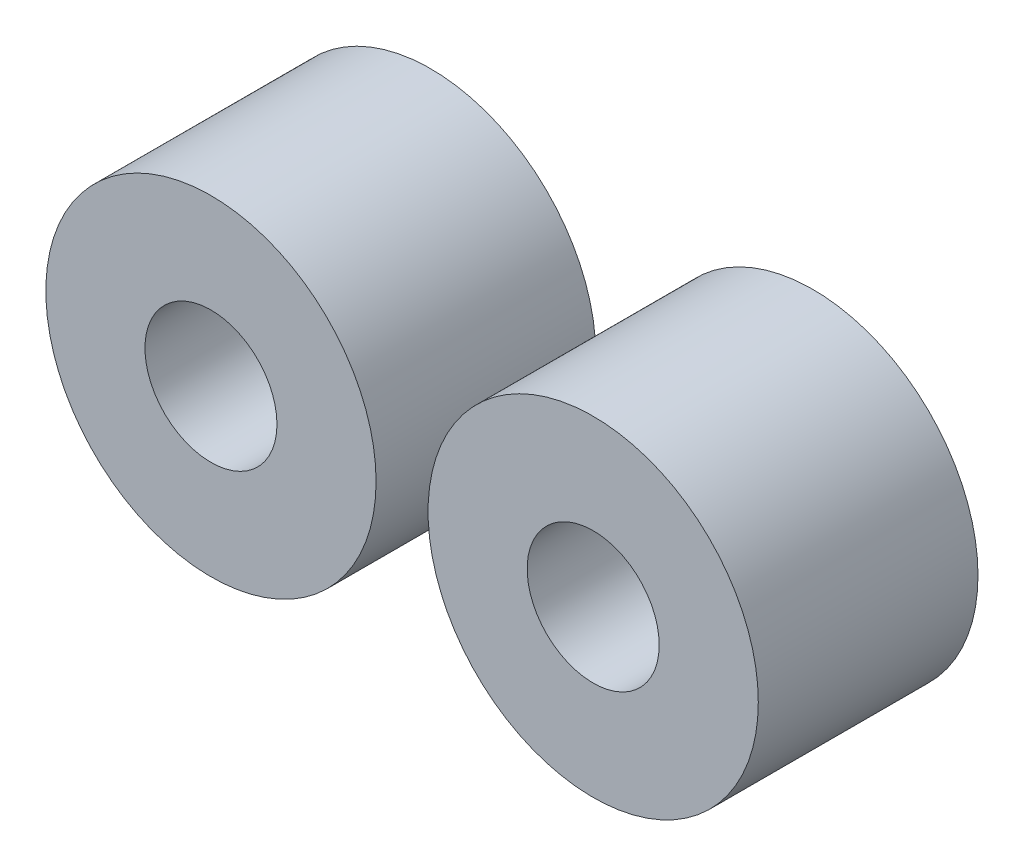
SolidWorks part; units mm, degrees
ref_plane "Płaszczyzna przednia" through (0, 0, 0) normal (0, 0, 1) x (1, 0, 0)
ref_plane "Płaszczyzna górna" through (0, 0, 0) normal (0, 1, 0) x (1, 0, 0)
ref_plane "Płaszczyzna prawa" through (0, 0, 0) normal (1, 0, 0) x (0, 0, -1)
sketch "Szkic1" plane through (0, 0, 0) normal (0, 0, 1) x (1, 0, 0)
  circle A0 centre (0, 0) radius 381
  circle A1 centre (0, 0) radius 953
  circle A2 centre (2206, 0) radius 953
  circle A3 centre (2206, 0) radius 381
  dimension "D1" = 762
  dimension "D2" = 1906
  dimension "D4" = 2206
extrude "Dodanie-wyciągnięcie2" add sketch "Szkic1" along normal blind 1268 contours A2 A3 | A1 A0 region at (-926.0451, 0, 0) region at (1279.9549, 0, 0)
ref_axis "Oś1" through (2206, 0, 1268) along (0, 0, -1)
ref_axis "Oś2" through (0, 0, 1268) along (0, 0, -1)
equation "\"D4@Szkic1\"=\"D2@Szkic1\"+300mm"
